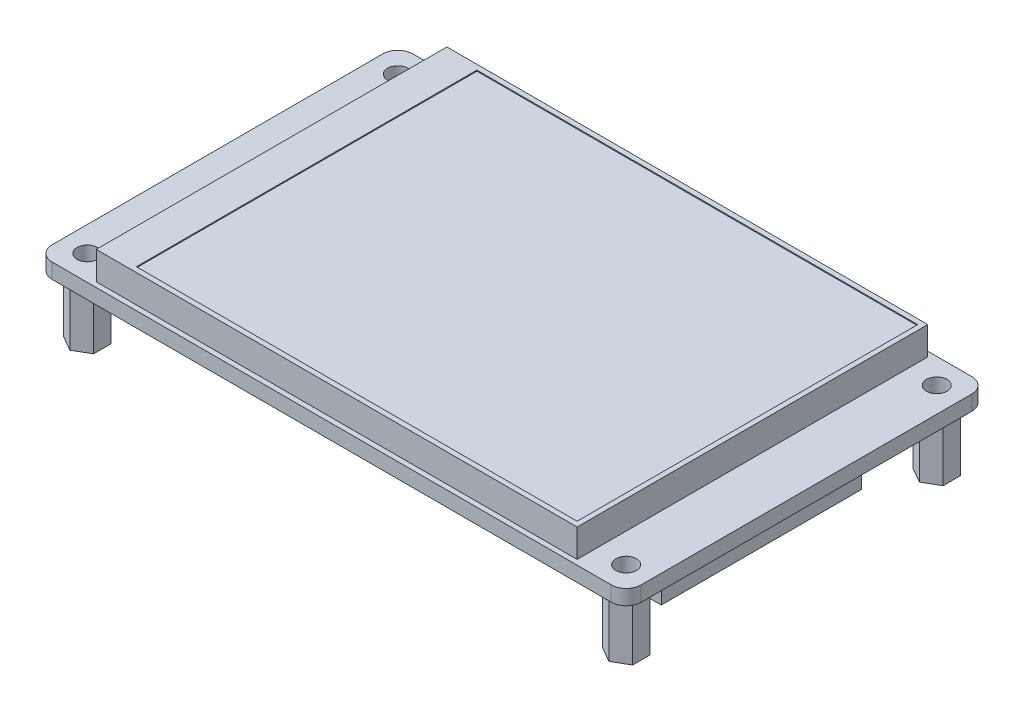
SolidWorks part; units mm, degrees
ref_plane "Front Plane" through (0, 0, 0) normal (0, 0, 1) x (1, 0, 0)
ref_plane "Top Plane" through (0, 0, 0) normal (0, 1, 0) x (1, 0, 0)
ref_plane "Right Plane" through (0, 0, 0) normal (1, 0, 0) x (0, 0, -1)
sketch "Sketch1" plane through (0, 0, 0) normal (0, 1, 0) x (1, 0, 0)
  line L1 (-24, -17.5) -> (24, -17.5)
  line L2 (-24, -17.5) -> (-24, 17.5)
  line L3 (-24, 17.5) -> (24, 17.5)
  line L4 (24, -17.5) -> (24, 17.5)
  line L5 (-24, -17.5) -> (24, 17.5) construction
  line L6 (-24, 17.5) -> (24, -17.5) construction
  line L7 (-29.4, -18) -> (29.4, -18)
  line L8 (-29.4, -18) -> (-29.4, 18)
  line L9 (-29.4, 18) -> (29.4, 18)
  line L10 (29.4, -18) -> (29.4, 18)
  line L11 (-29.4, -18) -> (29.4, 18) construction
  line L12 (-29.4, 18) -> (29.4, -18) construction
  point P0 (0, 0)
  point P6 (0, 0)
  dimension "D1" = 58.8
  dimension "D2" = 36
  dimension "D3" = 35
  dimension "D4" = 48
extrude "Boss-Extrude1" add sketch "Sketch1" against normal blind 1.5 contours L8 L9 L10 L7
extrude "Boss-Extrude2" add sketch "Sketch1<3>" along normal blind 2.8 contours L1 L4 L3 L2 region at (0, 0, 0)
sketch "Sketch1<3>" plane through (0, 0, 0) normal (0, 1, 0) x (1, 0, 0) same geometry as "Sketch1"
fillet "Fillet1" radius 1.5 4 edges at (-29.4, -0.75, 18) (-29.4, -0.75, -18) (29.4, -0.75, -18) (29.4, -0.75, 18)
sketch "Sketch3" plane through (0, 0, 0) normal (0, 1, 0) x (1, 0, 0)
  line L0 (-27.9, 18) -> (27.9, 18) construction
  line L1 (-26.9, 17.2321) -> (-28.4, 16.366)
  line L2 (-28.4, 16.366) -> (-28.4, 14.634)
  line L3 (-28.4, 14.634) -> (-26.9, 13.7679)
  line L4 (-26.9, 13.7679) -> (-25.4, 14.634)
  line L5 (-25.4, 14.634) -> (-25.4, 16.366)
  line L6 (-25.4, 16.366) -> (-26.9, 17.2321)
  line L7 (-29.4, -16.5) -> (-29.4, 16.5) construction
  circle A0 centre (-26.9, 15.5) radius 1.5 construction
  dimension "D1" = 2.5
  dimension "D2" = 2.5
  dimension "D3" = 3
extrude "Boss-Extrude3" add sketch "Sketch3" against normal blind 6 from surface starting at face at (0, -1.5, 0)
hole_wizard "M2.5x0.45 Tapped Hole1" positions "Sketch10" profile "Sketch7" tap size "M2.5x0.45" standard "ANSI Metric" end condition through all
sketch "Sketch10" plane through (0, -7.5, 0) normal (0, -1, 0) x (-1, 0, 0)
  line L2 (25.4, 16.366) -> (28.4, 14.634) construction
  point P0 (26.9, 15.5)
  point P17 (0, 0)
cosmetic thread "Hole Thread1" parameters "D2"=2.5
sketch "Sketch7" plane through (-26.9, -7.5, -15.5) normal (1, 0, 0) x (0, 0, -1)
  line L0 (0, 0) -> (0, 10.3)
  line L1 (0, 10.3) -> (1.025, 10.3)
  line L2 (1.025, 10.3) -> (1.025, 0.433)
  line L3 (1.025, 0.433) -> (1.275, 0)
  line L5 (1.275, 0) -> (0, 0)
  line L6 (-1.025, 0.433) -> (-1.275, 0) construction
  line L11 (0, -6.35) -> (0, 107.95) construction
  dimension "Thru Tap Drill Dia." = 2.05
  dimension "Thru Tap Drill Depth" = 10.3
  dimension "Near C'Sink Dia." = 2.55
  dimension "Near C'Sink Angle" = 60
sketch "Sketch5" plane through (0, 2.8, 0) normal (0, 1, 0) x (1, 0, 0)
  line L0 (24, -17.5) -> (24, 17.5) construction
  line L1 (23.5, -17) -> (-20.5, -17)
  line L2 (23.5, -17) -> (23.5, 17)
  line L3 (23.5, 17) -> (-20.5, 17)
  line L4 (-20.5, -17) -> (-20.5, 17)
  line L5 (23.5, -17) -> (-20.5, 17) construction
  line L6 (23.5, 17) -> (-20.5, -17) construction
  point P0 (1.5, 0)
  dimension "D1" = 34
  dimension "D2" = 44
  dimension "D3" = 0.5
extrude "Cut-Extrude2" cut sketch "Sketch5" against normal blind 0.1
mirror "Mirror2" about plane through (0, 0, 0) normal (0, 0, 1) of "Boss-Extrude3", "M2.5x0.45 Tapped Hole1"
cosmetic thread "Hole Thread2" parameters "D2"=2.5
mirror "Mirror3" about plane through (0, 0, 0) normal (1, 0, 0) of "Mirror2", "Boss-Extrude3", "M2.5x0.45 Tapped Hole1"
cosmetic thread "Hole Thread3" parameters "D2"=2.5
cosmetic thread "Hole Thread4" parameters "D2"=2.5
sketch "Sketch9" plane through (0, -1.5, 0) normal (0, -1, 0) x (1, 0, 0)
  line L0 (29.4, 16.5) -> (29.4, -16.5) construction
  line L1 (18.9, -10) -> (24.9, -10)
  line L2 (18.9, -10) -> (18.9, 10)
  line L3 (18.9, 10) -> (24.9, 10)
  line L4 (24.9, -10) -> (24.9, 10)
  line L5 (18.9, -10) -> (24.9, 10) construction
  line L6 (18.9, 10) -> (24.9, -10) construction
  point P0 (21.9, 0)
  dimension "D1" = 4.5
  dimension "D2" = 20
  dimension "D3" = 6
extrude "Boss-Extrude4" add sketch "Sketch9" along normal blind 5.75
